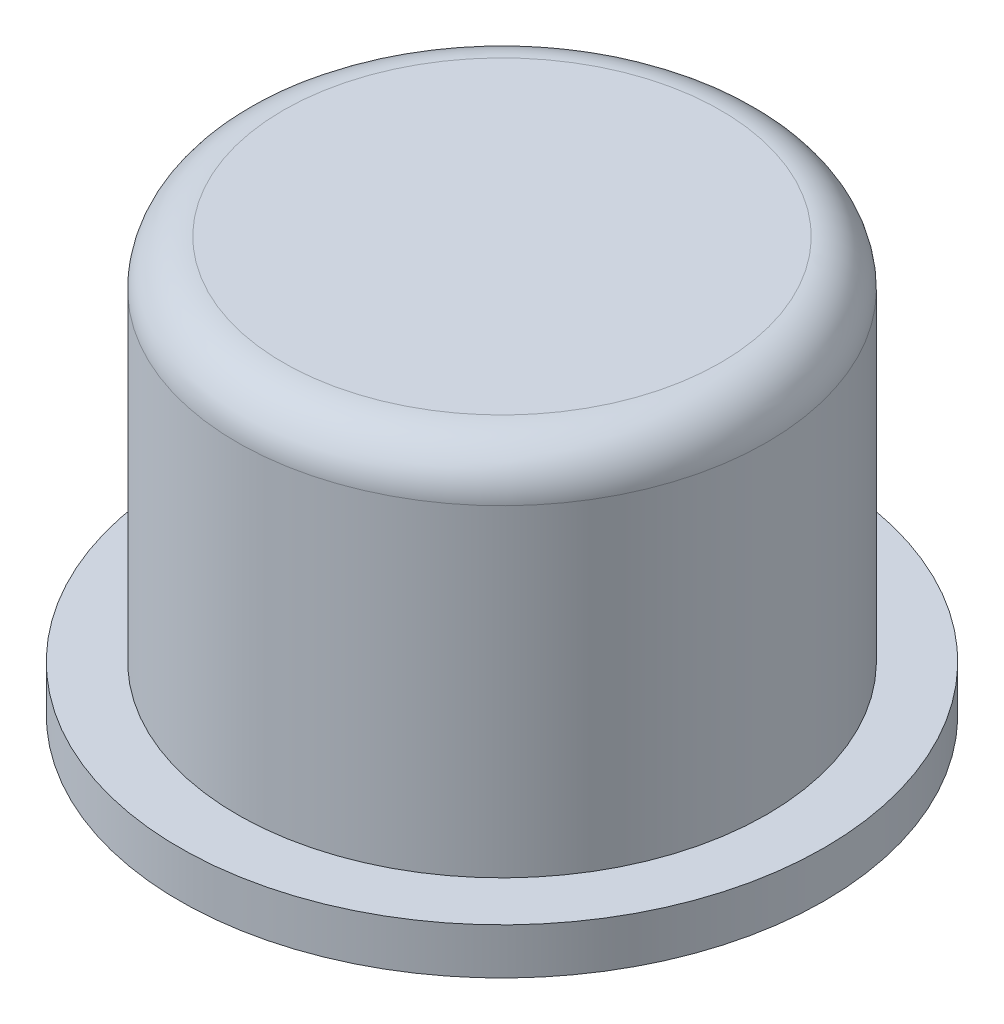
SolidWorks part; units mm, degrees
ref_plane "前视基准面" through (0, 0, 0) normal (0, 0, 1) x (1, 0, 0)
ref_plane "上视基准面" through (0, 0, 0) normal (0, 1, 0) x (1, 0, 0)
ref_plane "右视基准面" through (0, 0, 0) normal (1, 0, 0) x (0, 0, -1)
ref_plane "基准面5" through (0, 0, -3.85) normal (0, 0, 1) x (1, 0, 0)
sketch "草图2" plane through (0, 0, -3.85) normal (0, 0, 1) x (1, 0, 0)
  line L0 (1.9, 3.6) -> (0, 3.6)
  line L1 (0, 3.6) -> (0, 0)
  line L2 (0, 0) -> (2.8, 0)
  line L6 (2.3, 0.4) -> (2.3, 3.2)
  line L7 (0, 3.6) -> (0, 0) construction
  line L9 (2.3, 0.4) -> (2.8, 0.4)
  line L10 (2.8, 0.4) -> (2.8, 0)
  arc A0 (2.3, 3.2) -> (1.9, 3.6) centre (1.9, 3.2) ccw
  dimension "D1" = 0.4
  dimension "D2" = 2.3
  dimension "D4" = 2.8
  dimension "D6" = 0.4
  dimension "D7" = 3.6
revolve "旋转1" add sketch "草图2" angle 360 about L7 reverse direction yes
sketch "草图5" plane through (0, 0, 0) normal (0, -1, 0) x (1, 0, 0)
  circle A0 centre (0, -3.85) radius 2.8 construction
  circle A1 centre (0, -3.85) radius 2.8 construction
  circle A2 centre (0, -3.85) radius 1.85
  dimension "D1" = 3.7
extrude "切除-拉伸1" cut sketch "草图5" against normal blind 2.8
